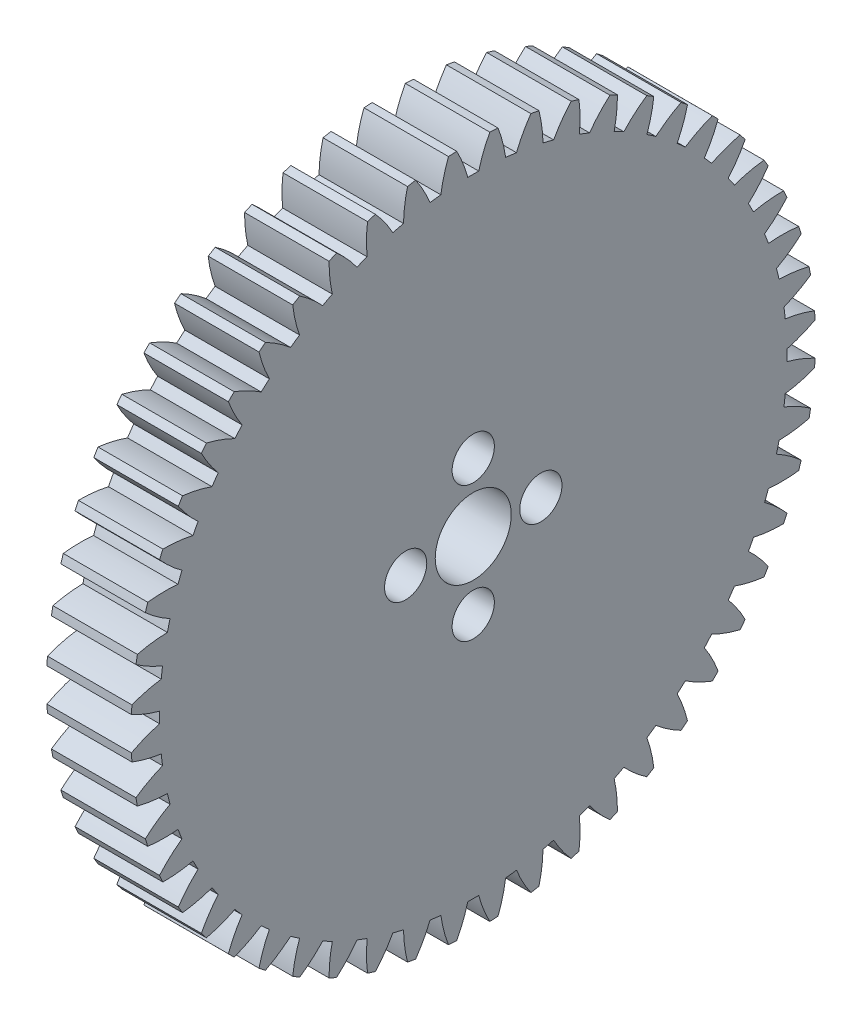
SolidWorks part; units mm, degrees
ref_plane "Plane1" through (0, 0, 0) normal (0, 0, 1) x (1, 0, 0)
ref_plane "Plane2" through (0, 0, 0) normal (0, 1, 0) x (1, 0, 0)
ref_plane "Plane3" through (0, 0, 0) normal (1, 0, 0) x (0, 0, -1)
sketch "HoldingSke" plane through (0, 0, 0) normal (0, 1, 0) x (1, 0, 0)
  line L0 (0, 0) -> (0.4104, -0.5253)
  line L1 (-15, 0) -> (100, 0) construction
  line L2 (0, 0) -> (-2.1039, 2.3779)
  line L3 (0, 0) -> (-11.863, 4.5341)
  line L4 (0, 0) -> (5.3169, 6.8053)
  line L5 (0, 0) -> (-46.8476, -17.4728)
  line L6 (0, 0) -> (-8.2896, -5.593)
  line L7 (-2.1039, 2.3779) -> (8.6586, 51.2059)
  line L8 (-76.2, 54.61) -> (-74.8, 54.61)
  line L9 (-71.009, 38.7566) -> (-53.1078, 45.2721)
  line L10 (-76.2, 71.12) -> (104.1128, 71.12)
  line L11 (0, 0) -> (-10, 0)
  line L12 (-76.2, 101.6) -> (-76.147, 101.6)
  line L13 (24.9733, 27.94) -> (52.9518, 28.4284)
  line L14 (24.9733, 27.94) -> (24.9743, 27.94)
  line L15 (24.9733, 27.94) -> (100.4006, 29.5858)
  line L16 (-63.627, -1.5) -> (-12.827, -1.5)
  circle A0 centre (0, 0) radius 4.5
  circle A1 centre (0, 0) radius 37.124
  circle A2 centre (0, 0) radius 37.5
  circle A3 centre (0, 0) radius 4.5
  dimension "Num_teeth" = 52
  dimension "Pitch_radius" = 180.3128
  dimension "Width" = 10
  dimension "Thickness" = 10
sketch "BasProSke" plane through (0, 0, 0) normal (0, 1, 0) x (1, 0, 0)
  line L0 (-10, 0) -> (60, 0) construction
  line L1 (0, 0) -> (0, 40.5)
  line L2 (0, 0) -> (10, 0)
  line L3 (10, 0) -> (10, 40.5)
  line L4 (10, 40.5) -> (0, 40.5)
  dimension "Thickness" = 10
  dimension "Diameter" = 81
revolve "Base-Revolve" add sketch "BasProSke" angle 360 about L0
sketch "TooCutSke" plane through (0, 0, 0) normal (1, 0, 0) x (0, 0, -1)
  line L1 (0, 0) -> (0, 107) construction
  line L2 (0, 0) -> (-1.2707, 38.9793) construction
  line L3 (0, 0) -> (-4.7077, 77.8275) construction
  line L4 (-1.2707, 38.9793) -> (-2.3538, 38.9138) construction
  arc A0 (0.6474, 37.1184) -> (-0.6474, 37.1184) centre (0, 0) ccw
  arc A1 (1.9744, 40.4773) -> (-1.9744, 40.4773) centre (0, 0) ccw
  circle A2 centre (0, 0) radius 39 construction
  circle A3 centre (0, 0) radius 36.648 construction
  arc A4 (-0.6474, 37.1184) -> (-1.9744, 40.4773) centre (-15.7221, 33.1043) ccw
  arc A5 (1.9744, 40.4773) -> (0.6474, 37.1184) centre (15.7221, 33.1043) ccw
extrude "ToothCut" cut sketch "TooCutSke" along normal through all
fillet "Breaks" [suppressed] radius 0.03 tangent propagation no
fillet "RootFillets" [suppressed] radius 0.376
pattern_circular "TeethCuts" count 52 over 360 about axis through (-10, 0, 0) along (1, 0, 0) of "ToothCut", "RootFillets", "Breaks"
sketch "HubNeaOneSke" plane through (0, 0, 0) normal (-1, 0, 0) x (0, 0, 1)
  circle A0 centre (0, 0) radius 37.124
  dimension "Diameter" = 74.248
extrude "HubNearOne" [suppressed] add sketch "HubNeaOneSke" along normal blind 40.0001
sketch "HubNeaBotSke" plane through (0, 0, 0) normal (-1, 0, 0) x (0, 0, 1)
  circle A0 centre (0, 0) radius 37.124
  dimension "Diameter" = 74.248
extrude "HubNearBoth" [suppressed] add sketch "HubNeaBotSke" along normal blind 20
ref_plane "FarPln" through (10, 0, 0) normal (1, 0, 0) x (0, 0, -1)
sketch "HubFarSke" plane through (10, 0, 0) normal (1, 0, 0) x (0, 0, -1)
  circle A0 centre (0, 0) radius 37.124
  dimension "Diameter" = 74.248
extrude "HubFar" [suppressed] add sketch "HubFarSke" along normal blind 20
sketch "BorSke" plane through (0, 0, 0) normal (1, 0, 0) x (0, 0, -1)
  circle A0 centre (0, 0) radius 4.5
  dimension "Diameter" = 9
extrude "Bore" cut sketch "BorSke" along normal mid plane 100.0001
sketch "KeySke" plane through (0, 0, 0) normal (1, 0, 0) x (0, 0, -1)
  line L0 (-1.5, 0) -> (-1.5, 5.9)
  line L1 (-1.5, 5.9) -> (1.5, 5.9)
  line L2 (1.5, 5.9) -> (1.5, 0)
  line L3 (0, 0) -> (0, 34) construction
  line L4 (-1.5, 0) -> (1.5, 0)
  dimension "Width" = 3
extrude "Keyway" [suppressed] cut sketch "KeySke" along normal mid plane 100.0001
pattern_circular "Keyway2" [suppressed] count 2 every 90 about axis through (-10, 0, 0) along (1, 0, 0) reverse direction yes
sketch "Esquisse2" plane through (0, 0, 0) normal (-1, 0, 0) x (0, 0, 1)
  circle A1 centre (8, 0) radius 1.125
  circle A4 centre (0, 0) radius 4.5 construction
  circle A5 centre (0, 0) radius 4.5 construction
  circle A6 centre (0, -8) radius 1.125
  circle A7 centre (-8, 0) radius 1.125
  circle A8 centre (0, 8) radius 1.125
  point P14 (0, 0)
  dimension "D1" = 2.25
  dimension "D3" = 4
  dimension "D2" = 8
extrude "Enlèv. mat.-Extru.1" cut sketch "Esquisse2" against normal up to next
sketch "Esquisse3" plane through (0, 0, 0) normal (-1, 0, 0) x (0, 0, 1)
  circle A0 centre (0, 0) radius 15
  circle A1 centre (0, -8) radius 1.125 construction
  circle A2 centre (8, 0) radius 1.125 construction
  circle A3 centre (0, 8) radius 1.125 construction
  circle A4 centre (-8, 0) radius 1.125 construction
  circle A5 centre (0, 0) radius 4.5 construction
  circle A6 centre (0, -8) radius 1.125
  circle A7 centre (8, 0) radius 1.125
  circle A8 centre (0, 8) radius 1.125
  circle A9 centre (-8, 0) radius 1.125
  circle A10 centre (0, 0) radius 4.5
  dimension "D1" = 30
extrude "Boss.-Extru.1" add sketch "Esquisse3" along normal blind 13
sketch "Esquisse4" plane through (10, 0, 0) normal (1, 0, 0) x (0, 0, -1)
  circle A0 centre (0, 8) radius 2.5
  circle A1 centre (8, 0) radius 2.5
  circle A2 centre (0, -8) radius 2.5
  circle A3 centre (-8, 0) radius 2.5
  dimension "D1" = 5
extrude "Enlèv. mat.-Extru.2" cut sketch "Esquisse4" against normal offset from surface (14 mm away) 9 up to face at (-13, 0, -6.875)
sketch "Esquisse6" plane through (0, 0, 0) normal (-1, 0, 0) x (0, 0, 1)
  circle A0 centre (0, 0) radius 35
  circle A1 centre (0, 0) radius 15 construction
  circle A2 centre (0, 0) radius 15
  dimension "D1" = 70
extrude "Enlèv. mat.-Extru.4" cut sketch "Esquisse6" against normal blind 6
sketch "Esquisse5" plane through (-13, 0, 0) normal (-1, 0, 0) x (0, 0, 1)
  circle A0 centre (0, 0) radius 10.5
  circle A1 centre (0, 0) radius 15 construction
  circle A2 centre (0, 0) radius 15
  dimension "D1" = 21
extrude "Enlèv. mat.-Extru.3" cut sketch "Esquisse5" against normal blind 5
chamfer "Chanfrein1" distance 4.5 angle 45 1 edges at (-8, 0, 15)
sketch "Esquisse7" plane through (6, 0, 0) normal (-1, 0, 0) x (0, 0, 1)
  circle A0 centre (0, 0) radius 4.5 construction
  circle A1 centre (0, 0) radius 4.5 construction
  text T0 "<b>52</b>"
  dimension "D1" = 30
  dimension "D2" = 3
extrude "Enlèv. mat.-Extru.5" cut sketch "Esquisse7" against normal blind 1.5
equation "' \"Module@HoldingSke\" = 6.35"
equation "' \"Num_teeth@HoldingSke\" = 12"
equation "' \"Ap@HoldingSke\" =  20"
equation "' \"Ap@HoldingSke\" = 20"
equation "' \"Width@HoldingSke\" = 0.5 * 25.4"
equation "' \"Hub_dia@HoldingSke\"= 1 * 25.4"
equation "' \"Hub_dia@HoldingSke\" = 1 * 25.4"
equation "' \"Overall_len@HoldingSke\" = 1.0 * 25.4"
equation "' \"Bore@HoldingSke\" = 0.75 * 25.4"
equation "' \"T_dim@HoldingSke\" = 0.1 * 25.4"
equation "' \"Width@KeySke\" = 0.25 * 25.4"
equation "' \"Show_teeth@HoldingSke\" = 13"
equation "' \"Backlash@HoldingSke\" = 0.009 * 25.4"
equation "' \"Addendum_fac@HoldingSke\" = 1.0"
equation "' \"Dedendum_fac@HoldingSke\" = 1.25"
equation "' \"Dedendum_add@HoldingSke\" = 0.00005 * 25.4"
equation "' \"Clearance_fac@HoldingSke\" = 0.25"
equation "\"Pitch@HoldingSke\" = 1 / \"Module@HoldingSke\""
equation "\"Overcut_dia@TooCutSke\" = (\"Num_teeth@HoldingSke\" + 2 * \"Addendum_fac@HoldingSke\") / \"Pitch@HoldingSke\" + 0.002 * 25.4"
equation "\"Pitch_dia@TooCutSke\" = \"Num_teeth@HoldingSke\" / \"Pitch@HoldingSke\""
equation "\"Base_dia@TooCutSke\" = \"Num_teeth@HoldingSke\" / \"Pitch@HoldingSke\" * cos((\"Ap@HoldingSke\"  * 3.14159265 / 180))"
equation "\"Root_dia@TooCutSke\" = (\"Num_teeth@HoldingSke\" + 2) / \"Pitch@HoldingSke\" - 2 * (\"Addendum_fac@HoldingSke\" + \"Dedendum_fac@HoldingSke\") / \"Pitch@HoldingSke\" - \"Dedendum_add@HoldingSke\" * 2"
equation "\"Half_ang@TooCutSke\" = 180 / \"Num_teeth@HoldingSke\""
equation "\"Half_CT@TooCutSke\" = \"Num_teeth@HoldingSke\" / \"Pitch@HoldingSke\" * sin((3.14159265 / 2 / \"Num_teeth@HoldingSke\")) / 2 - 7 * \"Backlash@HoldingSke\" / 4"
equation "\"Flank_rad@TooCutSke\" = \"Num_teeth@HoldingSke\" / \"Pitch@HoldingSke\" / 5"
equation "\"Radius@RootFillets\" = \"Clearance_fac@HoldingSke\" / \"Pitch@HoldingSke\" + \"Dedendum_add@HoldingSke\""
equation "\"Break_rad@Breaks\" = 0.02 / \"Pitch@HoldingSke\""
equation "\"Thickness@HoldingSke\" = \"Width@HoldingSke\""
equation "\"OAL@HoldingSke\" = \"Thickness@HoldingSke\""
equation "\"MHD@HoldingSke\" = (\"Num_teeth@HoldingSke\" + 2) / \"Pitch@HoldingSke\" - 2 * (\"Addendum_fac@HoldingSke\" + \"Dedendum_fac@HoldingSke\")  / \"Pitch@HoldingSke\" - \"Dedendum_add@HoldingSke\" * 2"
equation "\"MBD@HoldingSke\" = (\"Num_teeth@HoldingSke\" + 2) / \"Pitch@HoldingSke\" - 2 * (\"Addendum_fac@HoldingSke\" + \"Dedendum_fac@HoldingSke\")  / \"Pitch@HoldingSke\" - \"Dedendum_add@HoldingSke\" * 2 - 0.002 * 25.4"
equation "\"MHD@HoldingSke\" = ((sgn( \"MHD@HoldingSke\" - \"Hub_dia@HoldingSke\" )-1)*( \"MHD@HoldingSke\" - \"Hub_dia@HoldingSke\" ))/-2+ \"Hub_dia@HoldingSke\""
equation "\"MBD@HoldingSke\" = ((sgn( \"MBD@HoldingSke\" - \"Bore@HoldingSke\" )-1)*( \"MBD@HoldingSke\" - \"Bore@HoldingSke\" ))/-2+ \"Bore@HoldingSke\""
equation "\"OAL@HoldingSke\" = ((sgn( \"OAL@HoldingSke\" - \"Overall_len@HoldingSke\" )+1)*( \"OAL@HoldingSke\" - \"Overall_len@HoldingSke\" ))/2 + \"Overall_len@HoldingSke\" + 0.000002 * 25.4"
equation "\"Num_teeth@TeethCuts\" = int( \"Show_teeth@HoldingSke\" ) + 1"
equation "\"Num_teeth@TeethCuts\" = ((sgn( \"Num_teeth@TeethCuts\" - \"Num_teeth@HoldingSke\" )-1)*( \"Num_teeth@TeethCuts\" - \"Num_teeth@HoldingSke\" ))/-2+ \"Num_teeth@HoldingSke\""
equation "\"Num_teeth@TeethCuts\" = ((sgn( \"Num_teeth@TeethCuts\" - 2.0)+1)*( \"Num_teeth@TeethCuts\" - 2.0))/2 +2.0"
equation "\"Angle@TeethCuts\" = 360.0 / \"Num_teeth@HoldingSke\""
equation "\"Diameter@BasProSke\" = (\"Num_teeth@HoldingSke\" + 2 * \"Addendum_fac@HoldingSke\") / \"Pitch@HoldingSke\""
equation "\"Thickness@BasProSke\"  = \"Thickness@HoldingSke\""
equation "' \"Fillet_rad@BasProSke\" =  \"Thickness@HoldingSke\" * 0.05"
equation "' \"Fillet_rad@BasProSke\" = \"Thickness@HoldingSke\" * 0.05"
equation "\"MHD@HoldingSke\" = ((sgn( \"MHD@HoldingSke\" - \"Root_dia@TooCutSke\" )-1)*( \"MHD@HoldingSke\" - \"Root_dia@TooCutSke\" ))/-2+ \"Root_dia@TooCutSke\""
equation "\"Diameter@HubNeaOneSke\" = \"MHD@HoldingSke\""
equation "\"Length@HubNearOne\" = \"OAL@HoldingSke\" - \"Thickness@BasProSke\""
equation "\"Diameter@HubNeaBotSke\" = \"MHD@HoldingSke\""
equation "\"Length@HubNearBoth\" = ( \"OAL@HoldingSke\" - \"Thickness@BasProSke\" ) / 2.0"
equation "\"Thickness@FarPln\" = \"Thickness@BasProSke\""
equation "\"Diameter@HubFarSke\" = \"MHD@HoldingSke\""
equation "\"Length@HubFar\" = ( \"OAL@HoldingSke\" - \"Thickness@BasProSke\" ) / 2.0"
equation "\"Diameter@BorSke\" = \"MBD@HoldingSke\""
equation "\"D1@Bore\" = \"OAL@HoldingSke\" * 2.0"
equation "\"D1@Keyway\" = \"OAL@HoldingSke\" * 2.0"
equation "\"Offset@KeySke\" = \"T_dim@HoldingSke\" + \"MBD@HoldingSke\" / 2.0"
